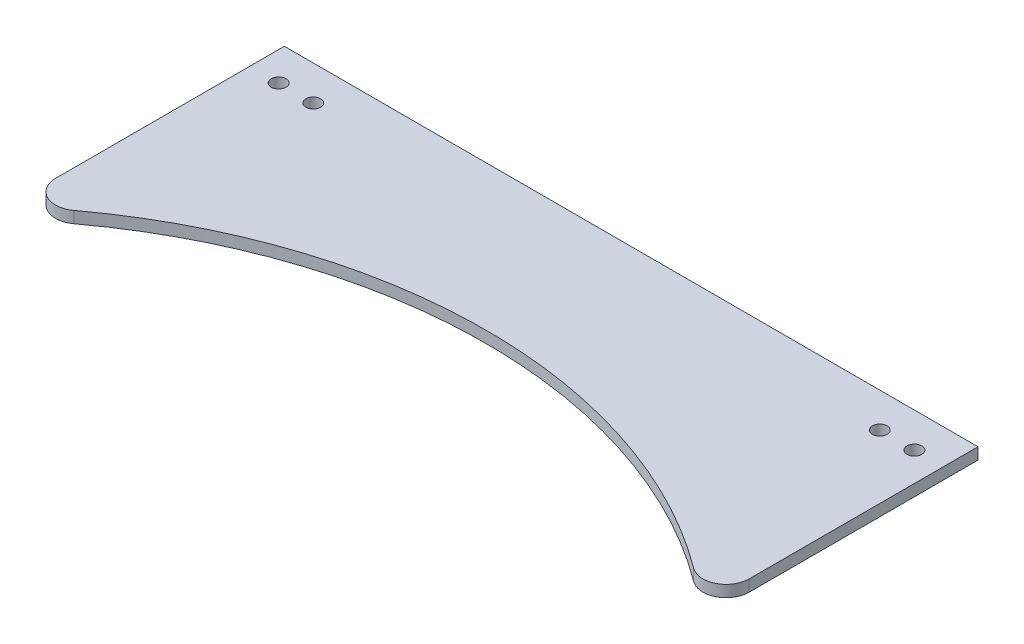
SolidWorks part; units mm, degrees
ref_plane "Front Plane" through (0, 0, 0) normal (0, 0, 1) x (1, 0, 0)
ref_plane "Top Plane" through (0, 0, 0) normal (0, 1, 0) x (1, 0, 0)
ref_plane "Right Plane" through (0, 0, 0) normal (1, 0, 0) x (0, 0, -1)
sketch "Sketch1" plane through (0, 0, 0) normal (0, 1, 0) x (1, 0, 0)
  line L0 (0, 0) -> (0, 76.2)
  line L1 (0, 76.2) -> (190.5, 76.2)
  line L2 (190.5, 76.2) -> (190.5, 0)
  arc A0 (0, 0) -> (190.5, 0) centre (95.25, -106.4927) cw
  dimension "D3" = 142.875
  dimension "D1" = 76.2
  dimension "D2" = 190.5
extrude "Boss-Extrude1" add sketch "Sketch1" along normal blind 3.175
sketch "Sketch3" plane through (0, 0, 0) normal (0, -1, 0) x (1, 0, 0)
  circle A0 centre (17.4625, -66.675) radius 2.032 construction
  circle A1 centre (7.9375, -66.675) radius 2.032 construction
  circle A2 centre (182.5625, -66.675) radius 2.032 construction
  circle A3 centre (173.0375, -66.675) radius 2.032 construction
  circle A4 centre (17.4625, -66.675) radius 2.032
  circle A5 centre (7.9375, -66.675) radius 2.032
  circle A6 centre (182.5625, -66.675) radius 2.032
  circle A7 centre (173.0375, -66.675) radius 2.032
extrude "Cut-Extrude1" cut sketch "Sketch3" against normal through all
fillet "Fillet1" radius 6.35 2 edges at (0, 1.5875, 0) (190.5, 1.5875, 0)
